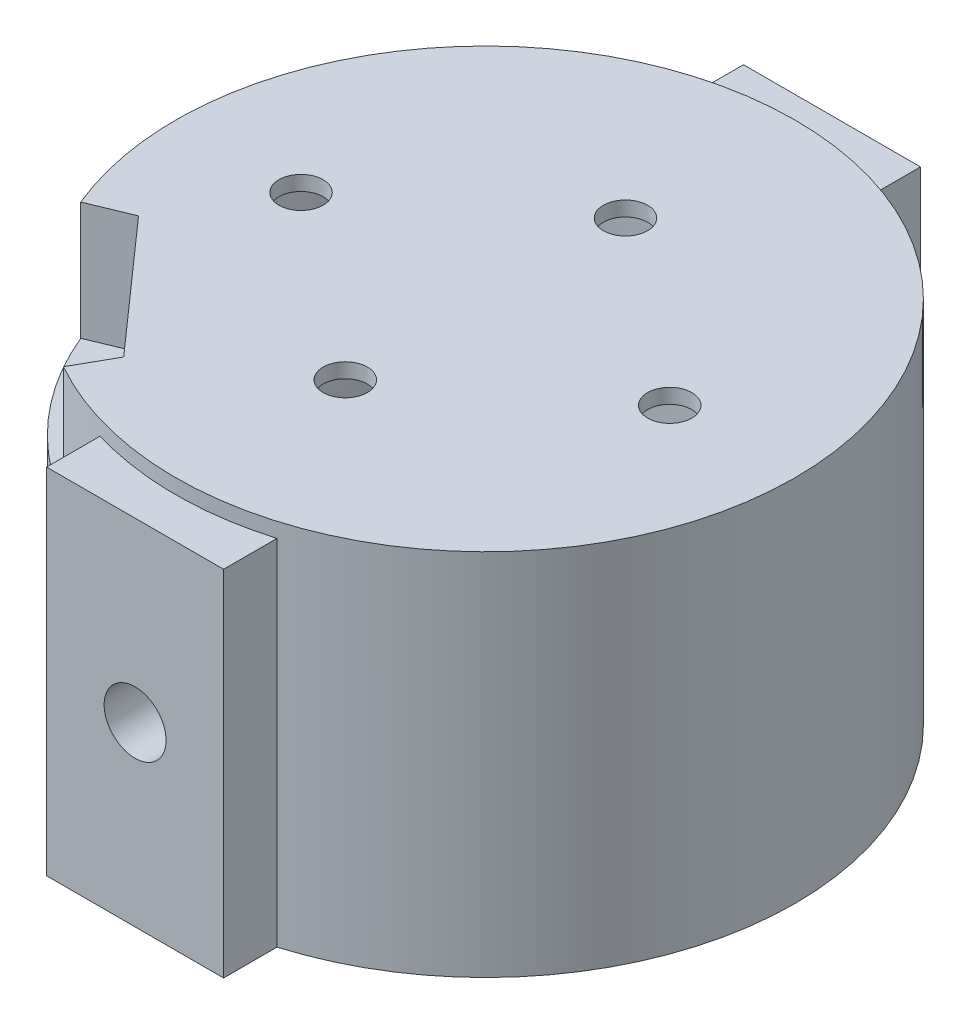
SolidWorks part; units mm, degrees
ref_plane "Front Plane" through (0, 0, 0) normal (0, 0, 1) x (1, 0, 0)
ref_plane "Top Plane" through (0, 0, 0) normal (0, 1, 0) x (1, 0, 0)
ref_plane "Right Plane" through (0, 0, 0) normal (1, 0, 0) x (0, 0, -1)
sketch "Sketch1" plane through (0, 0, 0) normal (0, 1, 0) x (1, 0, 0)
  circle A0 centre (0, 0) radius 17.75
  circle A1 centre (0, 0) radius 21
  dimension "D1" = 35.5
  dimension "D2" = 42
extrude "Boss-Extrude2" add sketch "Sketch1" along normal mid plane 24
sketch "Sketch5" plane through (0, 0, 0) normal (0, 1, 0) x (1, 0, 0)
  line L1 (-6, 17.5) -> (6, 17.5)
  line L2 (-6, 17.5) -> (-6, 23.5)
  line L3 (-6, 23.5) -> (6, 23.5)
  line L4 (6, 17.5) -> (6, 23.5)
  line L5 (-6, 17.5) -> (6, 23.5) construction
  line L6 (-6, 23.5) -> (6, 17.5) construction
  point P0 (0, 20.5)
  dimension "D1" = 12
  dimension "D2" = 6
extrude "Boss-Extrude7" add sketch "Sketch5" along normal mid plane 24 separate body
sketch "Sketch6" plane through (0, 0, 0) normal (0, 1, 0) x (1, 0, 0)
  line L1 (-6, -17.75) -> (6, -17.75)
  line L2 (-6, -17.75) -> (-6, -23.75)
  line L3 (-6, -23.75) -> (6, -23.75)
  line L4 (6, -17.75) -> (6, -23.75)
  line L5 (-6, -17.75) -> (6, -23.75) construction
  line L6 (-6, -23.75) -> (6, -17.75) construction
  circle A0 centre (0, 0) radius 17.75 construction
  point P0 (0, -20.75)
  dimension "D1" = 12
  dimension "D2" = 6
extrude "Boss-Extrude8" add sketch "Sketch6" along normal mid plane 24
sketch "Sketch7" plane through (0, 0, -23.5) normal (0, 0, -1) x (-1, 0, 0)
  circle A0 centre (0, 0) radius 2.1
  dimension "D1" = 4.2
extrude "Cut-Extrude1" cut sketch "Sketch7" against normal through all
sketch "Sketch8" plane through (0, 12, 0) normal (0, 1, 0) x (1, 0, 0)
  circle A0 centre (0, 0) radius 21
  dimension "D1" = 42
extrude "Boss-Extrude9" add sketch "Sketch8" along normal blind 1
sketch "Sketch9" plane through (0, 13, 0) normal (0, 1, 0) x (1, 0, 0)
  circle A0 centre (0, 0) radius 9.5 construction
  circle A2 centre (0, 9.5) radius 1.5
  circle A3 centre (0, -9.5) radius 1.5
  circle A4 centre (0, 0) radius 12.5 construction
  circle A5 centre (-12.5, 0) radius 1.5
  circle A6 centre (12.5, 0) radius 1.5
  dimension "D1" = 19
  dimension "D2" = 3
  dimension "D3" = 3
  dimension "D4" = 25
  dimension "D5" = 3
  dimension "D6" = 3
extrude "Cut-Extrude2" cut sketch "Sketch9" against normal up to next
sketch "Sketch12" plane through (0, 0, 0) normal (0, 1, 0) x (1, 0, 0)
  line L0 (-19.4037, -8.031) -> (-16.6317, -6.8837)
  line L1 (-10.3237, -18.2872) -> (-8.8489, -15.6747)
  line L2 (-8.8489, -15.6747) -> (-16.6317, -6.8837)
  arc A0 (-19.4037, -8.031) -> (-10.3237, -18.2872) centre (0, 0) ccw
  circle A1 centre (0, 0) radius 21 construction
  point P7 (0, 0)
  dimension "D2" = 3
  dimension "D1" = 3
extrude "Cut-Extrude6" cut sketch "Sketch12" along normal through all from offset 5
